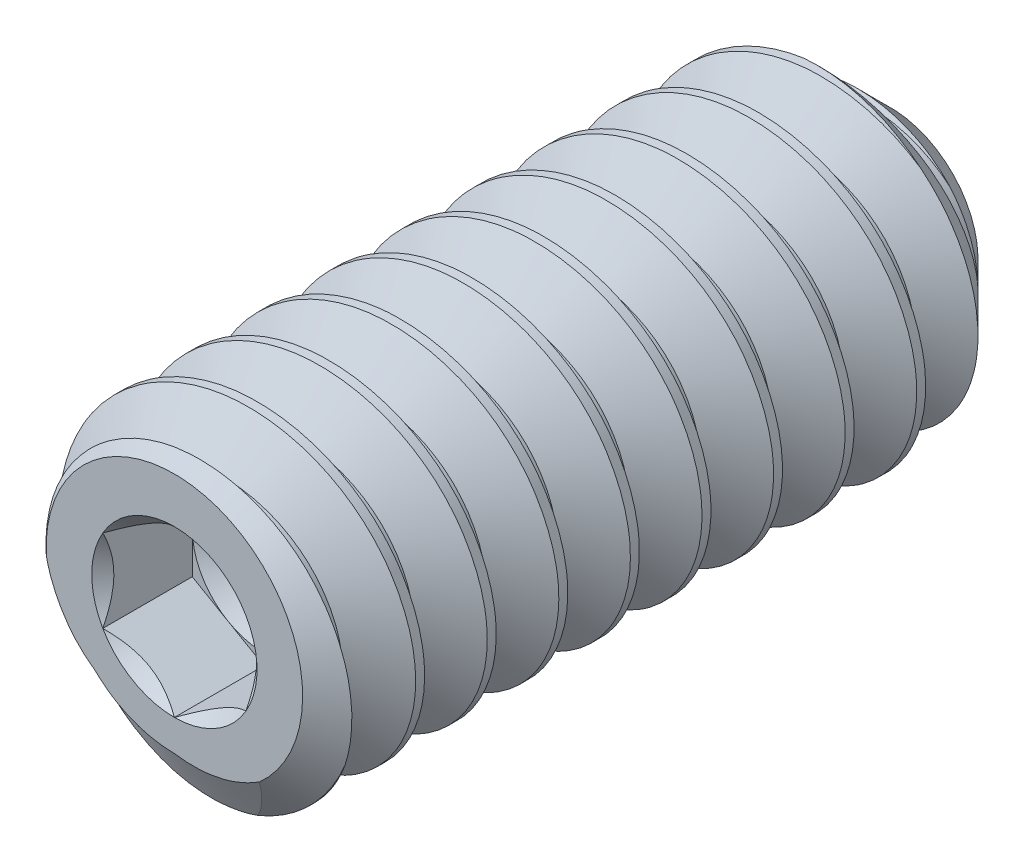
SolidWorks part; units mm, degrees
material "Plain Carbon Steel"
ref_plane "Front" through (0, 0, 0) normal (0, 0, 1) x (1, 0, 0)
ref_plane "Top" through (0, 0, 0) normal (0, 1, 0) x (1, 0, 0)
ref_plane "Right" through (0, 0, 0) normal (1, 0, 0) x (0, 0, -1)
sketch "Sketch22" plane through (0, 0, 0) normal (1, 0, 0) x (0, 0, -1)
  line L0 (-2.9408, 0) -> (-2.9408, 1.1379)
  line L1 (-2.9408, 1.1379) -> (-2.7416, 1.4224)
  line L2 (-2.7416, 1.4224) -> (2.7662, 1.4224)
  line L3 (2.7662, 1.4224) -> (3.4092, 0.7794)
  line L4 (3.4092, 0.7794) -> (2.9408, 0) construction
  line L5 (2.9408, 0) -> (-2.9408, 0)
  line L6 (2.9408, 0) -> (3.4092, 0) construction
  line L7 (3.4092, 0) -> (3.4092, 0.7794) construction
  line L8 (3.4092, -0.7794) -> (2.9408, 0) construction
  line L9 (-2.7416, -1.4224) -> (2.7662, -1.4224) construction
  line L10 (3.4092, 0.7794) -> (3.4092, 0)
  line L11 (3.4092, 0) -> (2.9408, 0)
  dimension "Dia" = 2.8448
  dimension "Length" = 6.35
  dimension "D3" = 35
  dimension "D5" = 118
  dimension "D6" = 45
  dimension "D7" = 2.2758
revolve "Revolve1" add sketch "Sketch22" angle 360 about L6
ref_plane "Plane1" through (0, 0, -3.4092) normal (0, 0, 1) x (1, 0, 0)
sketch "Sketch27" plane through (0, 0, -3.4092) normal (0, 0, 1) x (1, 0, 0)
  circle A0 centre (0, 0) radius 1.4224 construction
  circle A1 centre (0, 0) radius 1.4224
curve "Helix/Spiral1" pitch 0.635 height 6.985 radius 1.4224 centre (0, 0, -3.4092) axis (0, 0, 1) start towards (0, 1, 0)
sketch "Sketch28" plane through (0, 0, 0) normal (1, 0, 0) x (0, 0, -1)
  line L0 (3.4092, 1.4224) -> (3.9648, 1.4224)
  line L1 (3.9648, 1.4224) -> (3.7267, 1.01)
  line L2 (3.7267, 1.01) -> (3.6473, 1.01)
  line L3 (3.6473, 1.01) -> (3.4092, 1.4224)
  line L4 (3.5282, 1.2162) -> (3.8457, 1.2162) construction
  line L6 (-2.7416, 1.4224) -> (2.7662, 1.4224) construction
  line L7 (3.4092, 6.985) -> (3.4092, -6.985) construction
  dimension "D1" = 0.0794
  dimension "D3" = 60
  dimension "D2" = 0.3175
sweep "Cut-Sweep2" cut profiles "Sketch28" path "Helix/Spiral1" align with end faces yes
sketch "Sketch23" plane through (0, 0, 2.9408) normal (0, 0, 1) x (1, 0, 0)
  line L1 (0, 0.7332) -> (-0.635, 0.3666)
  line L2 (-0.635, 0.3666) -> (-0.635, -0.3666)
  line L3 (-0.635, -0.3666) -> (0, -0.7332)
  line L4 (0, -0.7332) -> (0.635, -0.3666)
  line L5 (0.635, -0.3666) -> (0.635, 0.3666)
  line L6 (0.635, 0.3666) -> (0, 0.7332)
  circle A0 centre (0, 0) radius 0.635 construction
  dimension "Hex" = 1.27
extrude "Cut-Extrude10" cut sketch "Sketch23" against normal blind 0.7937
sketch "Sketch24" plane through (0, 0, 2.9408) normal (0, 0, 1) x (1, 0, 0)
  circle A0 centre (0, 0) radius 0.7332
extrude "Cut-Extrude11" cut sketch "Sketch24" against normal through all draft 45
sketch "Sketch26" plane through (0, 0, 2.1471) normal (0, 0, 1) x (1, 0, 0)
  circle A0 centre (0, 0) radius 0.635 construction
  circle A1 centre (0, 0) radius 0.635
extrude "Cut-Extrude12" cut sketch "Sketch26" against normal through all draft 60
sketch "Sketch30" plane through (0, 0, 0) normal (1, 0, 0) x (0, 0, -1)
  line L0 (-2.7416, 1.4224) -> (2.7662, 1.4224) construction
  line L1 (-2.9408, 0) -> (-2.9408, 1.1379) construction
  line L2 (3.4092, 0) -> (3.4092, 0.7794) construction
  line L3 (-2.7416, -1.4224) -> (2.7662, -1.4224) construction
  point P0 (-2.9408, 1.4224)
  point P1 (3.4092, 1.4224)
  point P2 (3.4092, -1.4224)
  point P11 (1.1867, -1.4224)
  dimension "D1" = 2.2225
sketch "Sketch31" plane through (0, 0, 0) normal (1, 0, 0) x (0, 0, -1)
  line L2 (2.9408, 0) -> (3.4092, -0.7794)
  line L3 (3.4092, 0.7794) -> (2.9408, 0)
equation "\"D7@Sketch22\"=\"Dia@Sketch22\"*.8"
equation "\"D1@Sketch28\" = \"D4@Helix/Spiral1\" * .125"
equation "\"D3@Helix/Spiral1\" = \"Length@Sketch22\" + \"D4@Helix/Spiral1\""
equation "\"D1@Sketch30\" = \"D4@Helix/Spiral1\" * 3.5"
equation "\"hex Depth@Cut-Extrude10\" = \"Hex@Sketch23\" * .625"
equation "\"D2@Sketch28\" = \"D4@Helix/Spiral1\" * .5"
